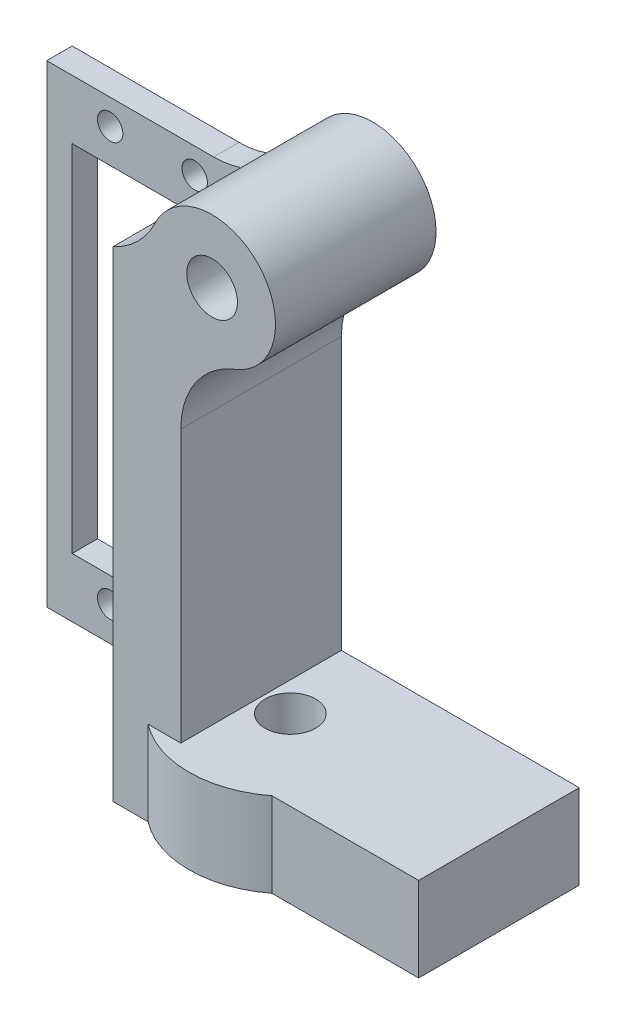
SolidWorks part; units mm, degrees
ref_plane "Plan de face" through (0, 0, 0) normal (0, 0, 1) x (1, 0, 0)
ref_plane "Plan de dessus" through (0, 0, 0) normal (0, 1, 0) x (1, 0, 0)
ref_plane "Plan de droite" through (0, 0, 0) normal (1, 0, 0) x (0, 0, -1)
sketch "Esquisse1" plane through (0, 0, 0) normal (0, 0, 1) x (1, 0, 0)
  line L1 (0, 0) -> (60, 0)
  line L2 (0, 0) -> (0, 56)
  line L3 (0, 56) -> (60, 56)
  line L4 (60, 0) -> (60, 56)
  line L5 (3, 49) -> (23, 49)
  line L6 (3, 49) -> (3, 7)
  line L7 (3, 7) -> (23, 7)
  line L8 (23, 49) -> (23, 7)
  line L9 (3, 49) -> (23, 7) construction
  line L10 (3, 7) -> (23, 49) construction
  point P5 (13, 28)
  dimension "D1" = 56
  dimension "D2" = 60
  dimension "D3" = 42
  dimension "D4" = 28
  dimension "D5" = 20
  dimension "D6" = 13
extrude "Boss.-Extru.1" add sketch "Esquisse1" along normal blind 3
sketch "Esquisse2" plane through (0, 0, 3) normal (0, 0, 1) x (1, 0, 0)
  line L1 (3, 7) -> (23, 7) construction
  circle A0 centre (7.5, 53) radius 1.5
  circle A1 centre (17.5, 53) radius 1.5
  circle A2 centre (7.5, 4) radius 1.5
  circle A3 centre (17.5, 4) radius 1.5
  dimension "D1" = 3
  dimension "D2" = 3
  dimension "D3" = 3
  dimension "D4" = 3
  dimension "D5" = 3
extrude "Enlèv. mat.-Extru.2" cut sketch "Esquisse2" against normal through all
sketch "Esquisse3" plane through (0, 0, 3) normal (0, 0, 1) x (1, 0, 0)
  line L0 (60, 56) -> (0, 56) construction
  line L1 (23.8619, 56) -> (31.8619, 56)
  line L2 (23.8619, 56) -> (23.8619, 0)
  line L3 (23.8619, 0) -> (60, 0)
  line L4 (60, 10) -> (60, 0)
  line L8 (60, 10) -> (31.8619, 10)
  line L9 (31.8619, 56) -> (31.8619, 10)
  dimension "D1" = 8
  dimension "D2" = 10
extrude "Boss.-Extru.2" add sketch "Esquisse3" along normal blind 16
sketch "Esquisse4" plane through (0, 0, 3) normal (0, 0, 1) x (1, 0, 0)
  line L1 (31.8619, 56) -> (60, 56)
  line L2 (31.8619, 56) -> (31.8619, 10)
  line L3 (31.8619, 10) -> (60, 10)
  line L4 (60, 56) -> (60, 10)
extrude "Enlèv. mat.-Extru.3" cut sketch "Esquisse4" against normal through all
sketch "Esquisse5" plane through (0, 0, 0) normal (0, 0, -1) x (-1, 0, 0)
  line L0 (-31.8619, 56) -> (-23.8619, 56) construction
  circle A0 centre (-35.5611, 58.5) radius 3
  circle A1 centre (-35.5611, 58.5) radius 7.5
  dimension "D1" = 15
  dimension "D2" = 6
  dimension "D3" = 11.6992
  dimension "D4" = 2.5
extrude "Boss.-Extru.3" add sketch "Esquisse5" against normal up to surface (19 mm away) up to face at (38.5746, 22, 19)
fillet "Congé1" radius 10 1 edges at (28.49, 56, 9.5)
fillet "Congé2" radius 10 1 edges at (31.8619, 51.9757, 9.5)
sketch "Esquisse8" plane through (0, 0, 0) normal (0, 0, -1) x (-1, 0, 0)
  line L0 (-35.5611, 58.5) -> (-35.5611, -5.0994) construction
sketch "Esquisse9" plane through (0, 0, 0) normal (0, -1, 0) x (1, 0, 0)
  line L0 (42.6497, 19) -> (27.9868, 19)
  line L1 (23.8619, 19) -> (60, 19) construction
  arc A0 (42.6497, 19) -> (27.9868, 19) centre (35.3182, 9.5) ccw
  dimension "D1" = 24
extrude "Boss.-Extru.4" add sketch "Esquisse9" against normal up to surface (10 mm away) up to face at (45.9309, 10, 9.5)
sketch "Esquisse10" plane through (0, 0, 0) normal (0, -1, 0) x (1, 0, 0)
  circle A0 centre (35.3182, 9.5) radius 3
  dimension "D1" = 6
extrude "Enlèv. mat.-Extru.4" cut sketch "Esquisse10" against normal up to surface (10 mm away) up to face at (42.3934, 10, 13.0833)
chamfer "Chanfrein1" distance 1 angle 45 1 edges at (23.8619, 28.4423, 3)
